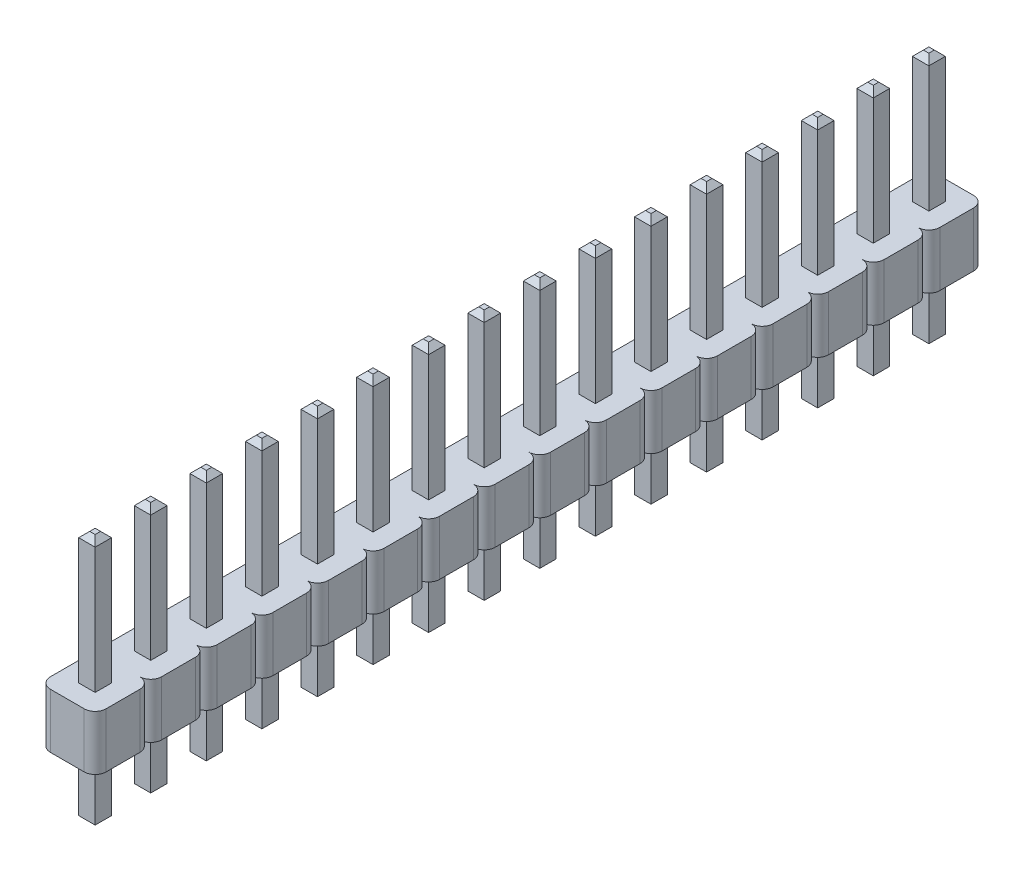
SolidWorks part; units mm, degrees
ref_plane "Front Plane" through (0, 0, 0) normal (0, 0, 1) x (1, 0, 0)
ref_plane "Top Plane" through (0, 0, 0) normal (0, 1, 0) x (1, 0, 0)
ref_plane "Right Plane" through (0, 0, 0) normal (1, 0, 0) x (0, 0, -1)
ref_plane "Plane1" through (0, 0, 0) normal (0, 1, 0) x (-1, 0, 0)
sketch "Sketch1" plane through (0, 0, 0) normal (0, 1, 0) x (-1, 0, 0)
  line L0 (-0.77, 1.27) -> (0.77, 1.27)
  line L1 (1.27, 0.77) -> (1.27, -0.77)
  line L2 (0.77, -1.27) -> (-0.77, -1.27)
  line L3 (-1.27, -0.77) -> (-1.27, 0.77)
  line L4 (-0.77, 0.77) -> (0.77, -0.77) construction
  arc A0 (1.27, 0.77) -> (0.77, 1.27) centre (0.77, 0.77) ccw
  arc A1 (0.77, -1.27) -> (1.27, -0.77) centre (0.77, -0.77) ccw
  arc A2 (-1.27, -0.77) -> (-0.77, -1.27) centre (-0.77, -0.77) ccw
  arc A3 (-0.77, 1.27) -> (-1.27, 0.77) centre (-0.77, 0.77) ccw
  dimension "D3" = 0.5
  dimension "D2" = 2.54
extrude "Boss-Extrude1" add sketch "Sketch1" along normal blind 2.5
ref_plane "Plane2" through (0.77, 0, 1.27) normal (-1, 0, 0) x (0, 0, 1)
ref_plane "Plane3" through (0.77, 0, 1.27) normal (0, -1, 0) x (0, 0, 1)
ref_axis "Axis1" through (0.77, 0, -79.63) along (0, 0, 1)
pattern_linear "LPattern1" count 16 spacing 2.54 along (0, 0, 1) of "Boss-Extrude1"
ref_plane "Plane4" through (0, 0, 0) normal (0, 1, 0) x (-1, 0, 0)
sketch "Sketch2" plane through (0, 0, 0) normal (0, 1, 0) x (-1, 0, 0)
  line L0 (-0.375, 0.375) -> (0.375, 0.375)
  line L1 (0.375, 0.375) -> (0.375, -0.375)
  line L2 (0.375, -0.375) -> (-0.375, -0.375)
  line L3 (-0.375, -0.375) -> (-0.375, 0.375)
  line L4 (-0.375, 0.375) -> (0.375, -0.375) construction
  dimension "D1" = 0.75
extrude "Boss-Extrude2" add sketch "Sketch2" along normal blind 8.5 and the other way blind 3
ref_plane "Plane5" through (0.3725, 0, 0.3725) normal (-1, 0, 0) x (0, 0, 1)
ref_plane "Plane6" through (0.3725, 0, 0.3725) normal (0, -1, 0) x (0, 0, 1)
ref_axis "Axis2" through (0.3725, 0, -80.5275) along (0, 0, 1)
chamfer "Chamfer1" distance 0.25 angle 45 8 edges at (0, -3, 0.375) (-0.375, -3, 0) (0.375, -3, 0) (0, -3, -0.375) (0, 8.5, 0.375) (-0.375, 8.5, 0) (0, 8.5, -0.375) (0.375, 8.5, 0)
pattern_linear "LPattern2" count 16 spacing 2.54 along (0, 0, 1) of "Boss-Extrude2", "Chamfer1"
ref_axis "Axis3" through (0, -3.575, 0) along (0, 1, 0)
sketch "Sketch3" plane through (0, -3, 0) normal (0, -1, 0) x (1, 0, 0)
  circle A0 centre (0, 0) radius 0.125
sketch "Sketch4" plane through (0, 8.5, 0) normal (0, 1, 0) x (1, 0, 0)
  circle A0 centre (0, -38.1) radius 0.125
